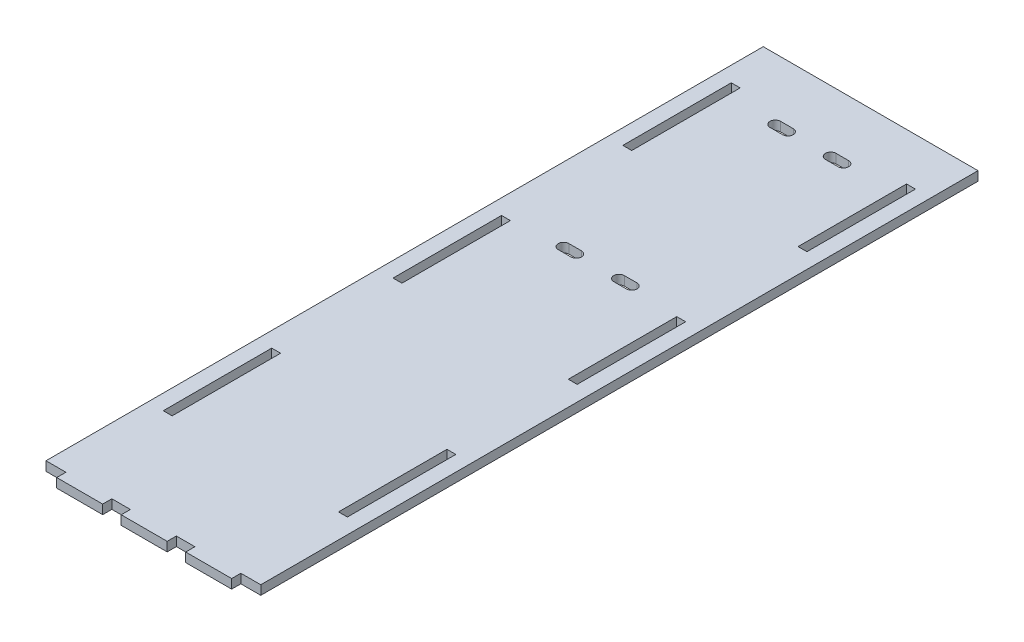
SolidWorks part; units mm, degrees
ref_plane "Front Plane" through (0, 0, 0) normal (0, 0, 1) x (1, 0, 0)
ref_plane "Top Plane" through (0, 0, 0) normal (0, 1, 0) x (1, 0, 0)
ref_plane "Right Plane" through (0, 0, 0) normal (1, 0, 0) x (0, 0, -1)
sketch "Sketch1" plane through (0, 0, 0) normal (0, 1, 0) x (1, 0, 0)
  line L16 (60.2, 0) -> (60.2, 160)
  line L17 (60.2, 160) -> (0, 160)
  line L22 (0, 160) -> (0, 0)
  line L23 (0, 0) -> (60.2, 0)
  line L24 (7.85, 152.55) -> (16.15, 152.55)
  line L25 (16.15, 145.65) -> (7.85, 145.65)
  line L32 (30.1, 160) -> (30.1, 0) construction
  line L33 (0, 80) -> (60.2, 80) construction
  line L34 (44.05, 145.65) -> (52.35, 145.65)
  line L35 (52.35, 152.55) -> (44.05, 152.55)
  line L36 (52.35, 7.45) -> (44.05, 7.45)
  line L37 (44.05, 14.35) -> (52.35, 14.35)
  line L38 (16.15, 14.35) -> (7.85, 14.35)
  line L39 (7.85, 7.45) -> (16.15, 7.45)
  arc A8 (7.85, 152.55) -> (7.85, 145.65) centre (7.85, 149.1) ccw
  arc A9 (16.15, 145.65) -> (16.15, 152.55) centre (16.15, 149.1) ccw
  arc A10 (52.35, 152.55) -> (52.35, 145.65) centre (52.35, 149.1) cw
  arc A11 (44.05, 145.65) -> (44.05, 152.55) centre (44.05, 149.1) cw
  arc A12 (44.05, 14.35) -> (44.05, 7.45) centre (44.05, 10.9) ccw
  arc A13 (52.35, 7.45) -> (52.35, 14.35) centre (52.35, 10.9) ccw
  arc A14 (7.85, 7.45) -> (7.85, 14.35) centre (7.85, 10.9) cw
  arc A15 (16.15, 14.35) -> (16.15, 7.45) centre (16.15, 10.9) cw
  dimension "D6" = 3.45
  dimension "D7" = 3.45
  dimension "D1" = 7.85
  dimension "D3" = 160
  dimension "D4" = 60.2
  dimension "D5" = 8.3
  dimension "D8" = 6.9
  dimension "D9" = 7.45
extrude "Boss-Extrude1" add sketch "Sketch1" along normal blind 6
sketch "Sketch2" plane through (0, 6, 0) normal (0, 1, 0) x (1, 0, 0)
  line L0 (0, 160) -> (0, 0) construction
  line L1 (-40, 189.1) -> (100.2, 189.1)
  line L2 (-40, 189.1) -> (-40, -279.1)
  line L3 (-40, -279.1) -> (100.2, -279.1)
  line L4 (100.2, 189.1) -> (100.2, -279.1)
  line L5 (-40, 189.1) -> (100.2, -279.1) construction
  line L6 (-40, -279.1) -> (100.2, 189.1) construction
  line L7 (60.2, 0) -> (60.2, 160) construction
  line L8 (44.05, 7.45) -> (52.35, 7.45) construction
  line L9 (7.85, 7.45) -> (16.15, 7.45) construction
  line L10 (16.15, 14.35) -> (7.85, 14.35) construction
  line L11 (7.85, 145.65) -> (16.15, 145.65) construction
  line L12 (16.15, 152.55) -> (7.85, 152.55) construction
  line L13 (44.05, 145.65) -> (52.35, 145.65) construction
  line L14 (52.35, 152.55) -> (44.05, 152.55) construction
  line L15 (44.05, 7.45) -> (52.35, 7.45)
  line L16 (7.85, 7.45) -> (16.15, 7.45)
  line L17 (16.15, 14.35) -> (7.85, 14.35)
  line L18 (7.85, 145.65) -> (16.15, 145.65)
  line L19 (16.15, 152.55) -> (7.85, 152.55)
  line L20 (44.05, 145.65) -> (52.35, 145.65)
  line L21 (52.35, 152.55) -> (44.05, 152.55)
  arc A0 (7.85, 14.35) -> (7.85, 7.45) centre (7.85, 10.9) ccw construction
  arc A1 (7.85, 152.55) -> (7.85, 145.65) centre (7.85, 149.1) ccw construction
  arc A2 (52.35, 7.45) -> (52.35, 14.35) centre (52.35, 10.9) ccw construction
  arc A3 (44.05, 14.35) -> (44.05, 7.45) centre (44.05, 10.9) ccw construction
  arc A4 (16.15, 7.45) -> (16.15, 14.35) centre (16.15, 10.9) ccw construction
  arc A5 (16.15, 145.65) -> (16.15, 152.55) centre (16.15, 149.1) ccw construction
  arc A6 (44.05, 152.55) -> (44.05, 145.65) centre (44.05, 149.1) ccw construction
  arc A7 (52.35, 145.65) -> (52.35, 152.55) centre (52.35, 149.1) ccw construction
  arc A8 (52.35, 7.45) -> (52.35, 14.35) centre (52.35, 10.9) ccw
  arc A9 (44.05, 14.35) -> (44.05, 7.45) centre (44.05, 10.9) ccw
  arc A10 (7.85, 14.35) -> (7.85, 7.45) centre (7.85, 10.9) ccw
  arc A11 (16.15, 7.45) -> (16.15, 14.35) centre (16.15, 10.9) ccw
  arc A12 (7.85, 152.55) -> (7.85, 145.65) centre (7.85, 149.1) ccw
  arc A13 (16.15, 145.65) -> (16.15, 152.55) centre (16.15, 149.1) ccw
  arc A14 (44.05, 152.55) -> (44.05, 145.65) centre (44.05, 149.1) ccw
  arc A15 (52.35, 145.65) -> (52.35, 152.55) centre (52.35, 149.1) ccw
  point P4 (30.1, -45)
  point P8 (4.4, 10.9)
  point P12 (4.4, 149.1)
  line M17 (44.05, 14.35) -> (52.35, 14.35)
  arc M18 (52.35, 14.35) -> (52.35, 7.45) centre (52.35, 10.9) cw
  line M19 (52.35, 7.45) -> (44.05, 7.45)
  arc M20 (44.05, 7.45) -> (44.05, 14.35) centre (44.05, 10.9) cw
  line M21 (16.15, 7.45) -> (7.85, 7.45)
  arc M22 (7.85, 7.45) -> (7.85, 14.35) centre (7.85, 10.9) cw
  line M23 (7.85, 14.35) -> (16.15, 14.35)
  arc M24 (16.15, 14.35) -> (16.15, 7.45) centre (16.15, 10.9) cw
  dimension "D1" = 290
  dimension "D2" = 40
  dimension "D3" = 40
  dimension "D4" = 40
extrude "Boss-Extrude2" add sketch "Sketch2" against normal blind 6 contours M17 M20 M19 M18 | M21 M24 M23 M22 | A14 L20 A15 L21 | L2 L1 L4 L3 | L18 A13 L19 A12 region at (48.2, 6, -10.9) region at (12, 6, -10.9)
sketch "Sketch3" plane through (0, 6, 0) normal (0, 1, 0) x (1, 0, 0)
  line L0 (30.1, 189.1) -> (30.1, 31.8238) construction
  line L1 (84.4, 158.2465) -> (90.2, 158.2465)
  line L2 (84.4, 158.2465) -> (84.4, 87.4465)
  line L3 (84.4, 87.4465) -> (90.2, 87.4465)
  line L4 (90.2, 158.2465) -> (90.2, 87.4465)
  line L5 (84.4, 158.2465) -> (90.2, 87.4465) construction
  line L6 (84.4, 87.4465) -> (90.2, 158.2465) construction
  line L7 (-40, 189.1) -> (100.2, 189.1) construction
  line L9 (-24.2, 87.4465) -> (-30, 87.4465)
  line L10 (-30, 158.2465) -> (-30, 87.4465)
  line L11 (-24.2, 158.2465) -> (-30, 158.2465)
  line L12 (-24.2, 158.2465) -> (-24.2, 87.4465)
  line L13 (100.2, 189.1) -> (100.2, -279.1) construction
  line L15 (-24.2, -62.5535) -> (-30, -62.5535)
  line L16 (-30, 8.2465) -> (-30, -62.5535)
  line L17 (-24.2, 8.2465) -> (-30, 8.2465)
  line L18 (-24.2, 8.2465) -> (-24.2, -62.5535)
  line L19 (84.4, 8.2465) -> (84.4, -62.5535)
  line L20 (84.4, 8.2465) -> (90.2, 8.2465)
  line L21 (90.2, 8.2465) -> (90.2, -62.5535)
  line L22 (84.4, -62.5535) -> (90.2, -62.5535)
  line L23 (-24.2, -212.5535) -> (-30, -212.5535)
  line L24 (-30, -141.7535) -> (-30, -212.5535)
  line L25 (-24.2, -141.7535) -> (-30, -141.7535)
  line L26 (-24.2, -141.7535) -> (-24.2, -212.5535)
  line L27 (84.4, -141.7535) -> (84.4, -212.5535)
  line L28 (84.4, -141.7535) -> (90.2, -141.7535)
  line L29 (90.2, -141.7535) -> (90.2, -212.5535)
  line L30 (84.4, -212.5535) -> (90.2, -212.5535)
  point P4 (87.3, 122.8465)
  dimension "D1" = 70.8
  dimension "D2" = 5.8
  dimension "D3" = 10
  dimension "D4" = 3
extrude "Cut-Extrude1" cut sketch "Sketch3" against normal blind 6
sketch "Sketch4" plane through (0, 6, 0) normal (0, 1, 0) x (1, 0, 0)
  line L1 (-27, -273.1) -> (3, -273.1) construction
  line L2 (-27, -273.1) -> (-27, -285.1) construction
  line L3 (-27, -279.1) -> (3, -279.1)
  line L4 (3, -273.1) -> (3, -285.1) construction
  line L5 (-27, -273.1) -> (3, -279.1) construction
  line L6 (-27, -279.1) -> (3, -273.1) construction
  line L8 (15.1, -273.1) -> (15.1, -285.1) construction
  line L9 (15.1, -273.1) -> (45.1, -273.1) construction
  line L10 (45.1, -273.1) -> (45.1, -285.1) construction
  line L11 (15.1, -279.1) -> (45.1, -279.1)
  line L12 (57.2, -273.1) -> (57.2, -285.1) construction
  line L13 (57.2, -273.1) -> (87.2, -273.1) construction
  line L14 (87.2, -273.1) -> (87.2, -285.1) construction
  line L15 (57.2, -279.1) -> (87.2, -279.1)
  line L16 (-40, -279.1) -> (100.2, -279.1) construction
  line L17 (100.2, 189.1) -> (100.2, -279.1) construction
  line L20 (-40, 189.1) -> (-40, -279.1) construction
  line L21 (57.2, -285.1) -> (87.2, -285.1)
  line L22 (15.1, -285.1) -> (45.1, -285.1)
  line L23 (-27, -285.1) -> (3, -285.1)
  line L24 (-27, -279.1) -> (-27, -285.1)
  line L25 (3, -279.1) -> (3, -285.1)
  line L26 (15.1, -279.1) -> (15.1, -285.1)
  line L27 (45.1, -279.1) -> (45.1, -285.1)
  line L28 (57.2, -279.1) -> (57.2, -285.1)
  line L29 (87.2, -279.1) -> (87.2, -285.1)
  point P4 (-12, -276.1)
  dimension "D2" = 13
  dimension "D3" = 13
  dimension "D4" = 12
  dimension "D1" = 3
extrude "Boss-Extrude3" add sketch "Sketch4" against normal blind 6
sketch "Sketch5" plane through (0, 6, 0) normal (0, 1, 0) x (1, 0, 0)
  line L0 (100.2, 189.1) -> (100.2, -279.1)
  dimension "D1" = 468.2
